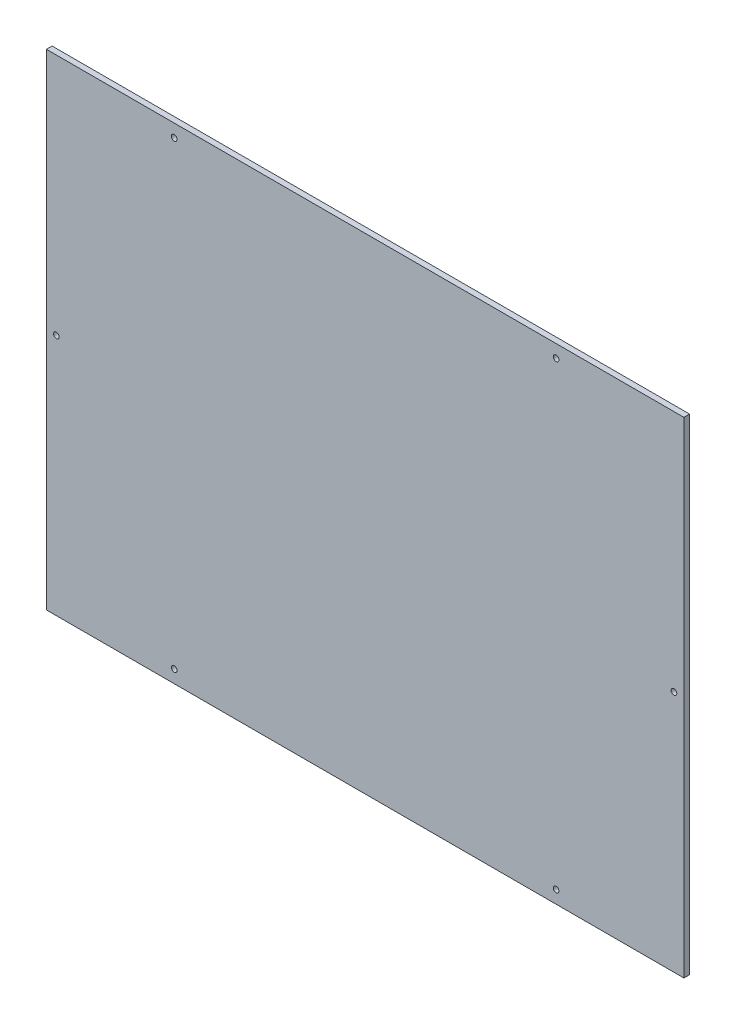
SolidWorks part; units mm, degrees
ref_plane "Piano frontale" through (0, 0, 0) normal (0, 0, 1) x (1, 0, 0)
ref_plane "Piano superiore" through (0, 0, 0) normal (0, 1, 0) x (1, 0, 0)
ref_plane "Piano destro" through (0, 0, 0) normal (1, 0, 0) x (0, 0, -1)
sketch "Schizzo1" plane through (0, 0, 0) normal (0, 0, 1) x (1, 0, 0)
  line L0 (-224.5, 351.6275) -> (-224.5, -66.2585) construction
  line L1 (0, 0) -> (-449, 0)
  line L2 (0, 0) -> (0, 342)
  line L3 (0, 342) -> (-449, 342)
  line L4 (-449, 0) -> (-449, 342)
  line L5 (-387.9788, 171) -> (120.8821, 171) construction
  circle A0 centre (-90, 333) radius 2
  circle A1 centre (-7, 171) radius 2
  circle A2 centre (-359, 333) radius 2
  circle A3 centre (-442, 171) radius 2
  circle A4 centre (-359, 9) radius 2
  circle A7 centre (-90, 9) radius 2
  point P9 (-224.5, 171)
  dimension "D3" = 4
  dimension "D1" = 449
  dimension "314" = 342
  dimension "D4" = 9
  dimension "D5" = 90
  dimension "D6" = 7
extrude "Estrusione-Estrusione1" add sketch "Schizzo1" along normal blind 4
